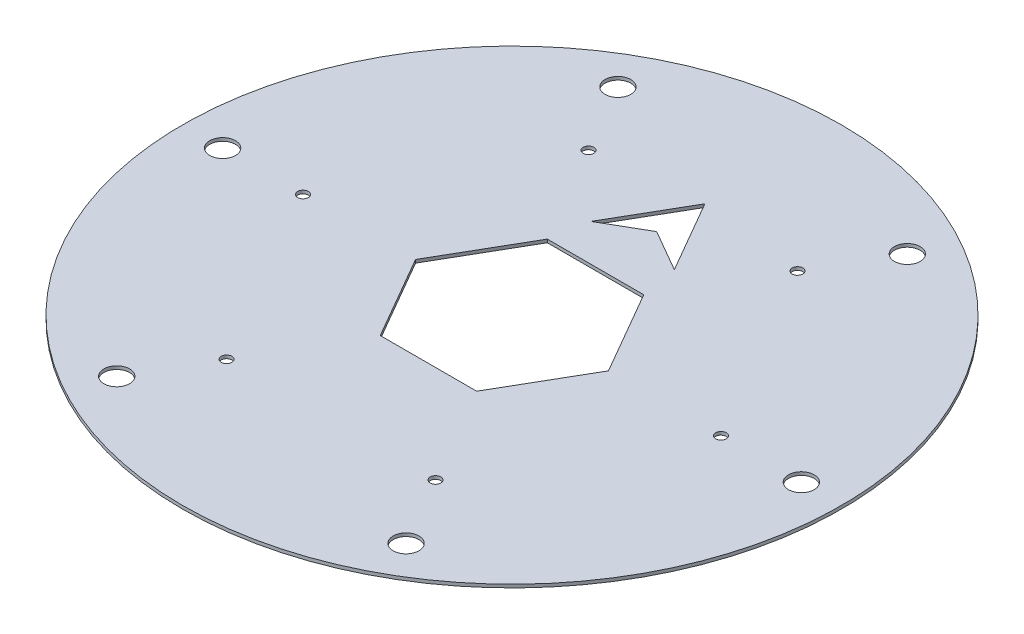
SolidWorks part; units mm, degrees
ref_plane "前视基准面" through (0, 0, 0) normal (0, 0, 1) x (1, 0, 0)
ref_plane "上视基准面" through (0, 0, 0) normal (0, 1, 0) x (1, 0, 0)
ref_plane "右视基准面" through (0, 0, 0) normal (1, 0, 0) x (0, 0, -1)
sketch "草图1" plane through (0, 0, 0) normal (0, 1, 0) x (1, 0, 0)
  line L0 (-12.9904, 37.5) -> (0, 60)
  line L1 (30, 0) -> (15, 25.9808)
  line L2 (15, 25.9808) -> (-15, 25.9808)
  line L3 (-15, 25.9808) -> (-30, 0)
  line L4 (-30, 0) -> (-15, -25.9808)
  line L5 (-15, -25.9808) -> (15, -25.9808)
  line L6 (15, -25.9808) -> (30, 0)
  line L7 (0, 60) -> (12.9904, 37.5)
  line L8 (12.9904, 37.5) -> (0, 45)
  line L9 (0, 45) -> (-12.9904, 37.5)
  circle A0 centre (0, 0) radius 102.5
  circle A1 centre (0, 0) radius 30 construction
  point P15 (0, 25.9808)
  dimension "D1" = 205
  dimension "D2" = 60
  dimension "D3" = 120
  dimension "D4" = 60
  dimension "D5" = 15
base flange "基体-法兰1" sketch "草图1" thickness 1 reverse thickness direction no parameters "D1"=0.7366
hole_wizard "Ø8.0 (8) 直径孔1" positions "草图8" profile "草图7" hole size "Ø8.0" standard "GB" end condition through all
sketch "草图8" plane through (0, 0, 0) normal (0, 1, 0) x (1, 0, 0)
  point P0 (-90, 0)
  dimension "D1" = 90
sketch "草图7" plane through (-90, 0, 0) normal (1, 0, 0) x (0, 0, 1)
  line L0 (0, 0) -> (0, 1)
  line L1 (0, 1) -> (4, 1)
  line L2 (4, 1) -> (4, 0)
  line L5 (4, 0) -> (0, 0)
  line L11 (0, -6.35) -> (0, 107.95) construction
  dimension "通孔孔直径" = 8
  dimension "通孔孔深度" = 1
pattern_circular "阵列(圆周)1" count 6 over 360 about axis through (0, 0, 0) along (0, 1, 0) of "Ø8.0 (8) 直径孔1"
hole_wizard "Ø3.3 (3.3) 直径孔1" positions "草图9" profile "草图10" hole size "Ø3.3" standard "GB" end condition through all
sketch "草图9" plane through (0, 0, 0) normal (0, 1, 0) x (1, 0, 0)
  line L1 (65, 0) -> (32.5, 56.2917)
  line L2 (32.5, 56.2917) -> (-32.5, 56.2917)
  line L3 (-32.5, 56.2917) -> (-65, 0)
  line L4 (-65, 0) -> (-32.5, -56.2917)
  line L5 (-32.5, -56.2917) -> (32.5, -56.2917)
  line L6 (32.5, -56.2917) -> (65, 0)
  circle A0 centre (0, 0) radius 65 construction
  point P5 (65, 0)
  point P6 (32.5, 56.2917)
  point P7 (-32.5, 56.2917)
  point P8 (-65, 0)
  point P9 (-32.5, -56.2917)
  point P10 (32.5, -56.2917)
  point P28 (0, 0)
  dimension "D1" = 130
sketch "草图10" plane through (32.5, 0, 56.2917) normal (1, 0, 0) x (0, 0, 1)
  line L0 (0, 0) -> (0, 1)
  line L1 (0, 1) -> (1.65, 1)
  line L2 (1.65, 1) -> (1.65, 0)
  line L5 (1.65, 0) -> (0, 0)
  line L11 (0, -6.35) -> (0, 107.95) construction
  dimension "通孔孔直径" = 3.3
  dimension "通孔孔深度" = 1
sketch "折弯-线1" [suppressed] plane through (0, 0, 0) normal (0, 1, 0) x (1, 0, 0)
sketch "边界框1" [suppressed] plane through (0, 0, 0) normal (0, 1, 0) x (1, 0, 0)
sheet metal parameters "钣金1" thickness 1 parameters "D1"=0.7366
flat pattern "平板型式1" [suppressed]
sketch "折弯-线2" plane through (0, 0, 0) normal (0, 1, 0) x (1, 0, 0)
sketch3d "边界框2" [suppressed]
  line L0 (102.6183, 102.3814, 0) -> (102.3815, -102.6183, 0) construction
  line L1 (-102.3814, 102.6183, 0) -> (-102.6183, -102.3814, 0) construction
  line L2 (102.6183, 102.3814, 0) -> (-102.3814, 102.6183, 0) construction
  line L3 (102.3815, -102.6183, 0) -> (-102.6183, -102.3814, 0) construction
sheet metal parameters "钣金2" thickness 1 parameters "D1"=0.7366
flat pattern "平板型式1"
sketch "折弯-线2" plane through (0, 0, 0) normal (0, 1, 0) x (1, 0, 0)
sketch3d "边界框2" [suppressed]
  line L0 (-102.6183, 102.3814, 0) -> (-102.3815, -102.6183, 0) construction
  line L1 (102.3814, 102.6183, 0) -> (102.6183, -102.3814, 0) construction
  line L2 (-102.6183, 102.3814, 0) -> (102.3814, 102.6183, 0) construction
  line L3 (-102.3815, -102.6183, 0) -> (102.6183, -102.3814, 0) construction
sheet metal parameters "钣金3" thickness 1 parameters "D1"=0.7366
flat pattern "平板型式1"
sketch "折弯-线2" plane through (0, 0, 0) normal (0, 1, 0) x (1, 0, 0)
sketch3d "边界框2" [suppressed]
  line L0 (-102.6183, 102.3814, 0) -> (-102.3815, -102.6183, 0) construction
  line L1 (102.3814, 102.6183, 0) -> (102.6183, -102.3814, 0) construction
  line L2 (-102.6183, 102.3814, 0) -> (102.3814, 102.6183, 0) construction
  line L3 (-102.3815, -102.6183, 0) -> (102.6183, -102.3814, 0) construction
sheet metal parameters "钣金5" thickness 1 parameters "D1"=0.7366
flat pattern "平板型式1"
sketch "折弯-线2" plane through (0, 0, 0) normal (0, 1, 0) x (1, 0, 0)
sketch3d "边界框2" [suppressed]
  line L0 (-102.6183, 102.3814, 0) -> (-102.3815, -102.6183, 0) construction
  line L1 (102.3814, 102.6183, 0) -> (102.6183, -102.3814, 0) construction
  line L2 (-102.6183, 102.3814, 0) -> (102.3814, 102.6183, 0) construction
  line L3 (-102.3815, -102.6183, 0) -> (102.6183, -102.3814, 0) construction
